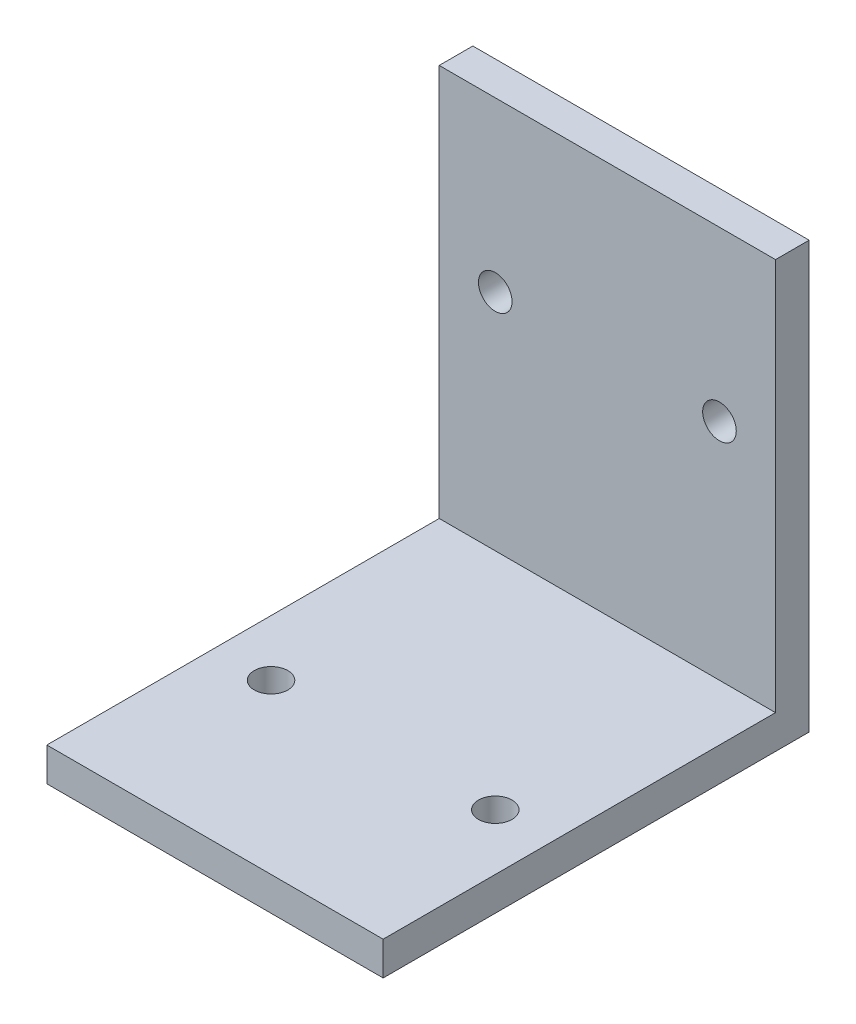
SolidWorks part; units mm, degrees
ref_plane "前视基准面" through (0, 0, 0) normal (0, 0, 1) x (1, 0, 0)
ref_plane "上视基准面" through (0, 0, 0) normal (0, 1, 0) x (1, 0, 0)
ref_plane "右视基准面" through (0, 0, 0) normal (1, 0, 0) x (0, 0, -1)
sketch "草图1" plane through (0, 0, 0) normal (0, 0, 1) x (1, 0, 0)
  line L1 (-15, 19) -> (15, 19)
  line L2 (-15, 19) -> (-15, -19)
  line L3 (-15, -19) -> (15, -19)
  line L4 (15, 19) -> (15, -19)
  line L5 (-15, 19) -> (15, -19) construction
  line L6 (-15, -19) -> (15, 19) construction
  point P0 (0, 0)
  dimension "D1" = 30
  dimension "D2" = 38
extrude "凸台-拉伸1" add sketch "草图1" along normal blind 3
sketch "草图2" plane through (0, 0, 3) normal (0, 0, 1) x (1, 0, 0)
  line L0 (15, -19) -> (15, 19) construction
  line L1 (-15, -19) -> (15, -19)
  line L2 (-15, -19) -> (-15, -16)
  line L3 (-15, -16) -> (15, -16)
  line L4 (15, -19) -> (15, -16)
  dimension "D1" = 3
extrude "凸台-拉伸2" add sketch "草图2" along normal blind 35
sketch "草图3" plane through (0, 0, 3) normal (0, 0, 1) x (1, 0, 0)
  line L0 (15, -16) -> (15, 19) construction
  line L1 (-15, 19) -> (-15, -16) construction
  line L2 (15, 19) -> (-15, 19) construction
  circle A0 centre (-10, 4) radius 1.5
  circle A1 centre (10, 4) radius 1.5
  dimension "D1" = 3
  dimension "D2" = 3
  dimension "D3" = 5
  dimension "D4" = 5
  dimension "D5" = 15
  dimension "D6" = 15
extrude "切除-拉伸1" cut sketch "草图3" against normal blind 35
sketch "草图4" plane through (0, -16, 0) normal (0, 1, 0) x (1, 0, 0)
  line L1 (15, -38) -> (15, -3) construction
  line L2 (-15, -38) -> (-15, -3) construction
  line L3 (15, -38) -> (-15, -38) construction
  circle A0 centre (-10, -23) radius 1.5
  circle A1 centre (10, -23) radius 1.5
  dimension "D1" = 3
  dimension "D2" = 3
  dimension "D3" = 5
  dimension "D4" = 5
  dimension "D5" = 15
extrude "切除-拉伸2" cut sketch "草图4" against normal blind 35
